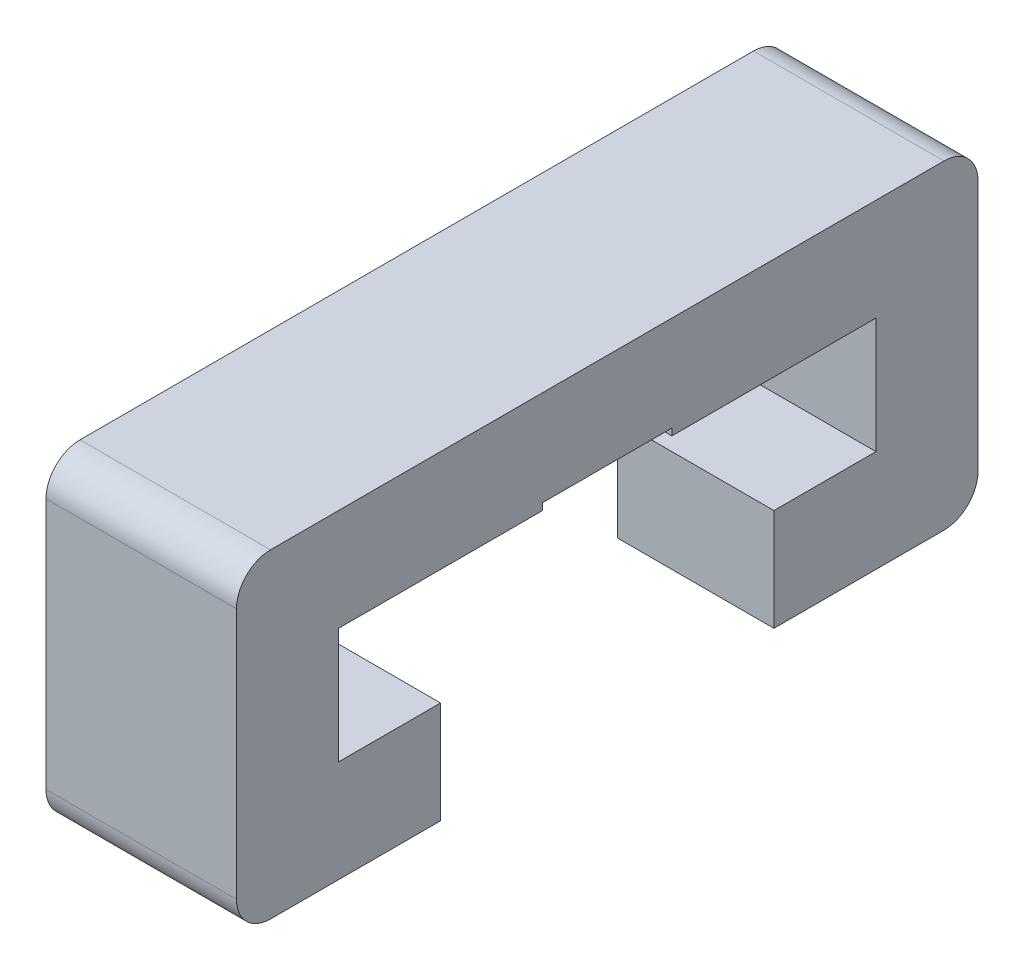
SolidWorks part; units mm, degrees
ref_plane "Front Plane" through (0, 0, 0) normal (0, 0, 1) x (1, 0, 0)
ref_plane "Top Plane" through (0, 0, 0) normal (0, 1, 0) x (1, 0, 0)
ref_plane "Right Plane" through (0, 0, 0) normal (1, 0, 0) x (0, 0, -1)
sketch "Locking slides" plane through (0, 0, 0) normal (0, 0, 1) x (1, 0, 0)
  line L0 (-52.5, 5.3) -> (-48, 5.3)
  line L1 (-51, 3.8) -> (-48, 3.8)
  line L2 (-51.4501, 8.7071) -> (-49.9501, 8.7071) construction
  line L3 (-54, 5.683) -> (-53.25, 5.25)
  line L6 (-48, 4.9) -> (-48, 2.15)
  line L7 (-48, 2.15) -> (-54, 2.15)
  line L9 (-52.5, 5.3) -> (-52.5, 2)
  line L12 (-51, 3.8) -> (-51, 2)
  line L13 (-51, 2) -> (-52.5, 2)
  line L14 (-48, 5.3) -> (-48, 3.8)
  line L15 (-51, 2) -> (-48, 2)
  line L16 (-48, 2) -> (-48, 3.8)
  line L17 (-54, 5.683) -> (-54, 2.15)
  line L18 (-48.5, 5.4) -> (-49.5, 5.4)
  line L19 (-49.5, 5.4) -> (-49.7598, 5.25)
  line L20 (-49.7598, 5.25) -> (-53.25, 5.25)
  line L21 (-48, 4.9) -> (-48.5, 5.4)
  line L22 (-49.5, 3.8) -> (-49.5, 3.5) construction
  line L23 (-49.9501, 8.7071) -> (-49.8501, 8.7071) construction
  line L25 (0, 21.25) -> (-54, 21.25) construction
  line L26 (0, 0) -> (0, 42.5) construction
  line L27 (-49.9501, 33.7929) -> (-49.8501, 33.7929) construction
  line L28 (-49.5, 38.7) -> (-49.5, 39) construction
  line L29 (-51.4501, 33.7929) -> (-49.9501, 33.7929) construction
  line L30 (-48, 37.6) -> (-48.5, 37.1)
  line L31 (-49.7598, 37.25) -> (-53.25, 37.25)
  line L32 (-49.5, 37.1) -> (-49.7598, 37.25)
  line L33 (-48.5, 37.1) -> (-49.5, 37.1)
  line L34 (-54, 36.817) -> (-54, 40.35)
  line L35 (-48, 40.5) -> (-48, 38.7)
  line L36 (-51, 40.5) -> (-48, 40.5)
  line L37 (-48, 37.2) -> (-48, 38.7)
  line L38 (-51, 40.5) -> (-52.5, 40.5)
  line L39 (-51, 38.7) -> (-51, 40.5)
  line L40 (-52.5, 37.2) -> (-52.5, 40.5)
  line L41 (-48, 40.35) -> (-54, 40.35)
  line L42 (-48, 37.6) -> (-48, 40.35)
  line L43 (-54, 36.817) -> (-53.25, 37.25)
  line L44 (-51, 38.7) -> (-48, 38.7)
  line L45 (-52.5, 37.2) -> (-48, 37.2)
  point P4 (-48, 5.4)
  point P30 (0, 0)
  point P54 (-48, 37.1)
sketch "Clip outline" plane through (0, 0, 0) normal (1, 0, 0) x (0, 0, -1)
  line L0 (-2.45, 2.2) -> (-4.95, 2.2)
  line L1 (-5.45, 2.7) -> (-5.45, 6.4)
  line L2 (-4.95, 6.9) -> (4.95, 6.9)
  line L8 (3.95, 5.4) -> (-3.95, 5.4)
  line L9 (-3.95, 5.4) -> (-3.95, 3.7)
  line L10 (-3.95, 3.7) -> (-2.45, 3.7)
  line L11 (-2.45, 3.7) -> (-2.45, 2.2)
  line L12 (0, 5.4) -> (0, 6.9) construction
  line L13 (-1.7131, 7.9732) -> (-1.6131, 7.9732) construction
  line L14 (-1.7131, 7.9732) -> (-3.2131, 7.9732) construction
  line L15 (-0.95, 5.4) -> (-0.95, 5.5)
  line L16 (-0.95, 5.5) -> (0.95, 5.5)
  line L17 (5.45, 2.7) -> (5.45, 6.4)
  line L18 (2.45, 2.2) -> (4.95, 2.2)
  line L19 (2.45, 3.7) -> (2.45, 2.2)
  line L20 (3.95, 3.7) -> (2.45, 3.7)
  line L21 (3.95, 5.4) -> (3.95, 3.7)
  line L22 (0.95, 5.4) -> (0.95, 5.5)
  line L23 (-13.2702, 0) -> (13.2702, 0) construction
  line L24 (0, -1.9846) -> (0, 14.382) construction
  arc A0 (-4.95, 2.2) -> (-5.45, 2.7) centre (-4.95, 2.7) cw
  arc A1 (-5.45, 6.4) -> (-4.95, 6.9) centre (-4.95, 6.4) cw
  arc A2 (5.45, 6.4) -> (4.95, 6.9) centre (4.95, 6.4) ccw
  arc A3 (4.95, 2.2) -> (5.45, 2.7) centre (4.95, 2.7) ccw
  point P20 (-5.45, 2.2)
  point P36 (0, 5.5)
  point P37 (0, 0)
  dimension "D8" = 0.5
  dimension "D1" = 1.5
  dimension "Tolerance" = 0.1
  dimension "D2" = 0.1
  dimension "D3" = 2.45
  dimension "Wall thickness" = 1.5
  dimension "D4" = 1.5
  dimension "D5" = 1.5
  dimension "D6" = 1.5
  dimension "D7" = 0.1
  dimension "D9" = 0.1
  dimension "D10" = 0.95
extrude "Boss-Extrude clip" add sketch "Clip outline" against normal blind 2.8 contours L18 A3 L17 A2 L2 A1 L1 A0 L0 L11 L10 L9 L8 L21 L20 L19 region at (0, 2.3187, 3.7)
sketch "Connecting lines" plane through (0, 0, 0) normal (1, 0, 0) x (0, 0, -1)
  line L0 (0, 6.15) -> (7.2416, 6.15)
  line L1 (0, 5.4) -> (0, 6.9) construction
  line L2 (3.95, 2.95) -> (3.95, 0)
  line L4 (2.45, 3.7) -> (2.45, 2.2) construction
  point P10 (0, 0)
  point P11 (2.45, 2.95)
  point P13 (0, 0)
  point P14 (0, 0)
extrude "Boss-Extrude clip notch" add sketch "Clip outline<3>" along normal blind 1.2402 from surface contours L8 L22 L16 L15 region at (0, 5.45, 0) starting at face at (-2.8, 4.41, 0)
sketch "Clip outline<3>" plane through (0, 0, 0) normal (1, 0, 0) x (0, 0, -1) same geometry as "Clip outline"
chamfer "Chamfer clip" distance 0.5 angle 45 7 edges at (-2.8, 2.95, -2.45) (-2.8, 3.7, -3.2) (-2.8, 4.55, -3.95) (-2.8, 5.4, 0) (-2.8, 4.55, 3.95) (-2.8, 3.7, 3.2) (-2.8, 2.95, 2.45)
extrude "Extrude-Thin connecting tabs" [suppressed] add sketch "Connecting lines" against normal blind 0.2 thin thin type mid plane wall 1
pattern_linear "LPattern clip grid" [suppressed] count 14 spacing 12 along (0, 0, -1) count 23 spacing 6 along (0, -1, 0) of bodies 102
equation "\"D2@Clip outline\" = \"Tolerance@Clip outline\""
equation "\"D3@Clip outline\"=\"Tolerance@Clip outline\" * 2 + \"Wall thickness@Clip outline\" * 1.5"
equation "\"D1@Clip outline\"=\"Wall thickness@Clip outline\""
equation "\"Tolerance@Clip outline\"=\"Tolerance@Locking slides@Enclosure master-1.Part\""
equation "\"Wall thickness@Clip outline\"=\"Base width@Locking slides@Enclosure master-1.Part\""
equation "\"D4@Clip outline\"=\"Wall thickness@Clip outline\""
equation "\"D5@Clip outline\"=\"Wall thickness@Clip outline\""
equation "\"D6@Clip outline\"=\"Wall thickness@Clip outline\""
equation "\"D7@Clip outline\"=\"Tolerance@Clip outline\""
equation "\"D9@Clip outline\"=\"Tolerance@Clip outline\""
equation "\"D10@Clip outline\"=\"Wall thickness@Clip outline\"/2 + \"Tolerance@Clip outline\"*2"
equation "\"D1@Boss-Extrude clip\" = \"Wall thickness@Clip outline\" * 2 - \"Tolerance@Clip outline\" * 2"
equation "\"D1@Boss-Extrude clip notch\" = \"Clip notch size@Locking slides@Enclosure master<1>.Part\""
